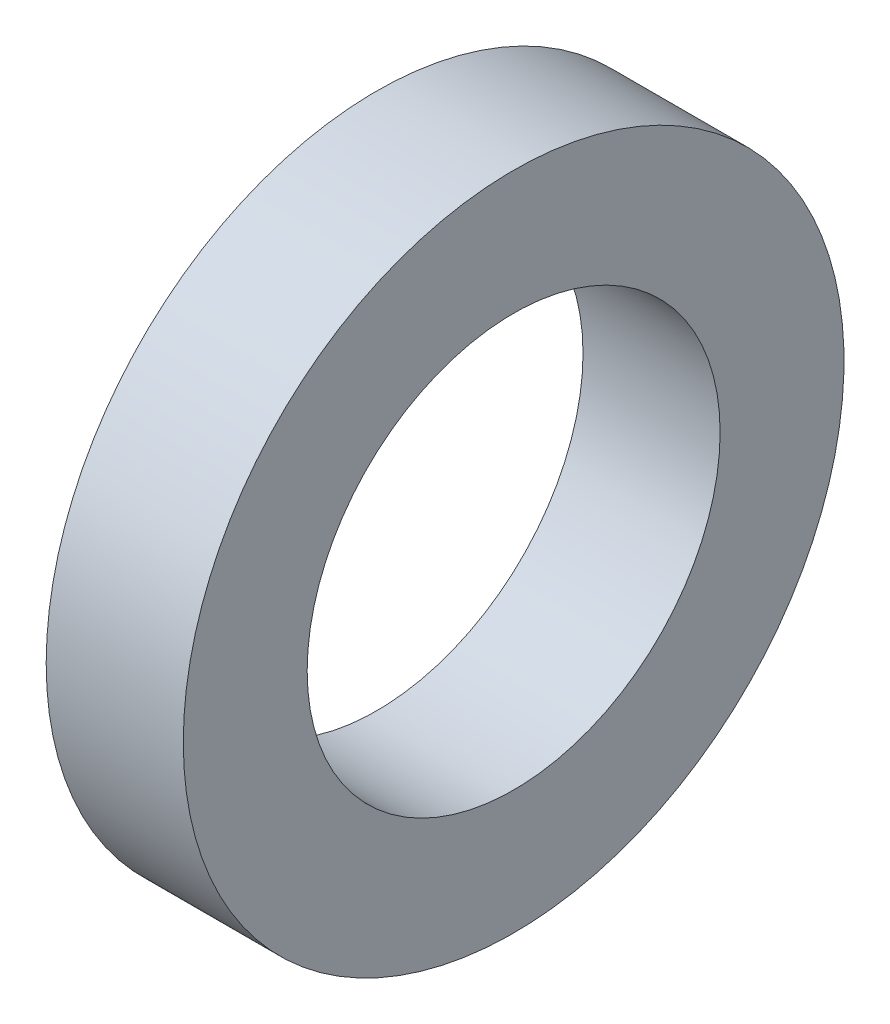
SolidWorks part; units mm, degrees
ref_plane "Front Plane" through (0, 0, 0) normal (0, 0, 1) x (1, 0, 0)
ref_plane "Top Plane" through (0, 0, 0) normal (0, 1, 0) x (1, 0, 0)
ref_plane "Right Plane" through (0, 0, 0) normal (1, 0, 0) x (0, 0, -1)
sketch "Sketch2" plane through (0, 0, 0) normal (0, 0, 1) x (1, 0, 0)
  line L0 (0, 0) -> (58.591, 0) construction
  line L2 (0, 0) -> (18.4, 0)
  line L3 (0, 0) -> (0, 2.5)
  line L4 (0, 2.5) -> (18.4, 2.5)
  line L5 (18.4, 0) -> (18.4, 2.5)
  line L6 (6.0094, 2.5) -> (6.0094, 6)
  line L11 (6.0094, 6) -> (9.9794, 6)
  line L16 (12.9794, 6) -> (12.9794, 3)
  line L17 (12.9794, 3) -> (13.6398, 3)
  line L18 (13.6398, 3) -> (13.6398, 2.5)
  line L19 (13.6398, 2.5) -> (6.0094, 2.5)
  line L22 (13.6398, 2.5) -> (16.1198, 2.5)
  line L23 (13.6398, 2.5) -> (13.6398, 4)
  line L24 (13.6398, 4) -> (16.1198, 4)
  line L25 (16.1198, 2.5) -> (16.1198, 4)
  line L27 (6.0094, 6) -> (9.9794, 6)
  line L28 (6.0094, 6) -> (6.0094, 9)
  line L29 (6.0094, 9) -> (9.9794, 9)
  line L30 (9.9794, 6) -> (9.9794, 9)
  line L31 (6.0094, 9) -> (6.0094, 8.25)
  line L32 (6.0094, 8.25) -> (5.0094, 8.25)
  line L33 (8.6609, 22.001) -> (8.6609, 12.476) construction
  line L34 (5.0094, 12.476) -> (12.3124, 12.476)
  line L35 (9.9794, 9) -> (12.3124, 9)
  line L36 (5.0094, 7.9375) -> (1.8344, 7.9375)
  line L37 (5.0094, 8.25) -> (5.0094, 12.476)
  line L38 (5.0094, 7.9375) -> (5.0094, 13.9365)
  line L39 (5.0094, 13.9365) -> (1.8344, 13.9365)
  line L40 (1.8344, 7.9375) -> (1.8344, 13.9365)
  line L41 (5.0094, 22.001) -> (12.3124, 22.001)
  line L42 (5.0094, 22.001) -> (5.0094, 30.1625)
  line L43 (5.0094, 30.1625) -> (12.3124, 30.1625)
  line L44 (12.3124, 22.001) -> (12.3124, 30.1625)
  line L49 (16.6398, 22.001) -> (16.6398, 7.5)
  line L51 (23.0198, 7.5) -> (23.0198, 6.5)
  line L54 (16.1198, 4) -> (13.6398, 4)
  line L56 (18.0398, 7.5) -> (23.0198, 7.5)
  line L57 (13.3124, 22.001) -> (16.6398, 22.001)
  line L58 (16.1198, 3.5) -> (20.0198, 3.5)
  line L59 (29.9098, 14) -> (26.9098, 11)
  line L60 (4.0094, 31.75) -> (18.0398, 31.75)
  line L61 (18.0398, 7.5) -> (23.0198, 7.5)
  line L62 (18.0398, 7.5) -> (18.0398, 12)
  line L63 (18.0398, 12) -> (23.0198, 12)
  line L64 (23.0198, 7.5) -> (23.0198, 12)
  line L65 (18.0398, 31.75) -> (18.0398, 12)
  line L66 (23.0198, 11) -> (26.9098, 11)
  line L67 (34.8098, 23) -> (31.3098, 19.5)
  line L68 (35.8098, 31) -> (38.7998, 33.99)
  line L69 (29.9098, 14) -> (29.9098, 15)
  line L70 (29.9098, 15) -> (22.9398, 15)
  line L71 (22.9398, 15) -> (21.0398, 15)
  line L72 (18.0398, 7.5) -> (16.6398, 7.5)
  line L73 (21.0398, 15) -> (21.0398, 43)
  line L74 (19.5798, 40) -> (9.6198, 40)
  line L75 (9.6198, 40) -> (4.0094, 40)
  line L76 (21.0398, 43) -> (19.5798, 43)
  line L77 (22.9398, 15) -> (29.9098, 15)
  line L78 (22.9398, 15) -> (22.9398, 21)
  line L79 (22.9398, 21) -> (29.9098, 21)
  line L80 (29.9098, 15) -> (29.9098, 21)
  line L81 (9.6198, 40) -> (19.5798, 40)
  line L82 (9.6198, 40) -> (9.6198, 50)
  line L83 (9.6198, 50) -> (19.5798, 50)
  line L84 (19.5798, 40) -> (19.5798, 50)
  line L85 (4.0094, 40) -> (4.0094, 31.75)
  line L86 (12.9794, 3) -> (12.9794, 2.5)
  line L87 (31.3098, 19.5) -> (29.9098, 19.5)
  line L88 (21.4694, 63.5) -> (21.4694, 51.308)
  line L89 (21.4694, 63.5) -> (25.9398, 63.5)
  line L90 (25.9398, 63.5) -> (25.9398, 25)
  line L91 (27.8398, 25) -> (25.9398, 25)
  line L92 (9.6198, 48) -> (8.1598, 48)
  line L93 (8.1598, 48) -> (8.1598, 53.476)
  line L94 (8.1598, 53.476) -> (19.5798, 53.476)
  line L95 (19.5798, 53.476) -> (19.5798, 50)
  line L96 (13.8698, 63.001) -> (13.8698, 53.476) construction
  line L97 (8.1598, 63.001) -> (19.5798, 63.001)
  line L98 (8.1598, 63.001) -> (8.1598, 68.2625)
  line L99 (8.1598, 68.2625) -> (19.5798, 68.2625)
  line L100 (19.5798, 63.001) -> (19.5798, 68.2625)
  line L101 (12.9794, 6) -> (11.9794, 6)
  line L102 (8.1598, 44.825) -> (4.9848, 44.825)
  line L103 (8.1598, 44.825) -> (8.1598, 54.9365)
  line L104 (8.1598, 54.9365) -> (4.9848, 54.9365)
  line L106 (9.9794, 6) -> (10.8794, 6)
  line L107 (27.8398, 25) -> (34.8098, 25)
  line L108 (34.8098, 25) -> (34.8098, 23)
  line L109 (0, 0) -> (-2, 0)
  line L110 (0, 0) -> (0, 11)
  line L111 (27.8398, 25) -> (34.8098, 25)
  line L112 (27.8398, 25) -> (27.8398, 32.5)
  line L113 (27.8398, 32.5) -> (34.8098, 32.5)
  line L114 (34.8098, 25) -> (34.8098, 32.5)
  line L115 (35.8098, 31) -> (34.8098, 31)
  line L116 (27.8398, 32.5) -> (27.8398, 64.5)
  line L117 (20.5373, 74.025) -> (6.2023, 74.025)
  line L118 (6.2023, 74.025) -> (6.2023, 76.2)
  line L119 (38.7998, 47.29) -> (30.8398, 55.25)
  line L120 (0, 11) -> (-2, 11)
  line L121 (38.7998, 43.815) -> (30.8623, 43.815)
  line L123 (-4.8152, 69.85) -> (1.5348, 76.2)
  line L124 (38.7998, 47.29) -> (38.7998, 33.99)
  line L125 (-2, 0) -> (-2, 11)
  line L126 (38.7998, 37.465) -> (30.8623, 37.465)
  line L127 (30.8623, 43.815) -> (30.8623, 37.465)
  line L128 (6.0094, 2.5) -> (6.0094, 0)
  line L129 (-0.0152, 63.5) -> (-0.0152, 30)
  line L132 (4.9848, 63.5) -> (-0.0152, 63.5)
  line L136 (-1.8152, 30) -> (-11.7752, 30)
  line L138 (-13.7752, 25.4) -> (-2, 25.4)
  line L139 (-2, 25.4) -> (-2, 11.5)
  line L140 (27.8398, 64.5) -> (20.5373, 64.5)
  line L141 (-1.8152, 30) -> (-11.7752, 30)
  line L142 (-1.8152, 30) -> (-1.8152, 39)
  line L143 (-1.8152, 39) -> (-11.7752, 39)
  line L144 (-11.7752, 30) -> (-11.7752, 39)
  line L145 (20.5373, 64.5) -> (20.5373, 74.025)
  line L146 (-12.7752, 37) -> (-12.7752, 47.29)
  line L147 (-12.7752, 37) -> (-11.7752, 37)
  line L148 (30.8398, 55.25) -> (30.8398, 76.2)
  line L149 (11.9794, 6) -> (11.9794, 5.45)
  line L154 (-2, 11.5) -> (0.5, 11.5)
  line L155 (4.9848, 60.6197) -> (24.0348, 60.6197)
  line L160 (4.9848, 60.6197) -> (4.9848, 55.8572)
  line L161 (4.9848, 55.8572) -> (24.0348, 55.8572)
  line L166 (24.0348, 60.6197) -> (24.0348, 55.8572)
  line L167 (4.9848, 60.6197) -> (24.0348, 55.8572) construction
  line L172 (4.9848, 55.8572) -> (24.0348, 60.6197) construction
  line L173 (24.0348, 62.2072) -> (25.9398, 62.2072)
  line L174 (11.9794, 5.45) -> (10.8794, 5.45)
  line L175 (10.8794, 6) -> (10.8794, 5.45)
  line L176 (24.0348, 62.2072) -> (24.0348, 54.2697)
  line L177 (24.0348, 54.2697) -> (25.9398, 54.2697)
  line L178 (25.9398, 62.2072) -> (25.9398, 54.2697)
  line L179 (24.0348, 62.2072) -> (25.9398, 54.2697) construction
  line L180 (24.0348, 54.2697) -> (25.9398, 62.2072) construction
  line L181 (3, 19.6197) -> (15.7, 19.6197)
  line L182 (3, 19.6197) -> (3, 14.8572)
  line L183 (3, 14.8572) -> (15.7, 14.8572)
  line L184 (15.7, 19.6197) -> (15.7, 14.8572)
  line L185 (3, 19.6197) -> (15.7, 14.8572) construction
  line L186 (3, 14.8572) -> (15.7, 19.6197) construction
  line L187 (15.7, 21.2072) -> (16.6398, 21.2072)
  line L188 (15.7, 21.2072) -> (15.7, 13.2697)
  line L189 (15.7, 13.2697) -> (16.6398, 13.2697)
  line L190 (16.6398, 21.2072) -> (16.6398, 13.2697)
  line L191 (15.7, 21.2072) -> (16.6398, 13.2697) construction
  line L192 (15.7, 13.2697) -> (16.6398, 21.2072) construction
  line L193 (0.5, 11.5) -> (0.5, 6.9375)
  line L194 (0.5, 6.9375) -> (1.8344, 6.9375)
  line L195 (23.0198, 6.5) -> (20.0198, 3.5)
  line L196 (4.9848, 63.5) -> (4.9848, 54.9365)
  line L197 (3, 43.825) -> (4.9848, 43.825)
  line L198 (1.8344, 6.9375) -> (1.8344, 7.9375)
  line L199 (6.0094, 0) -> (12.9794, 0)
  line L200 (12.9794, 0) -> (12.9794, 2.5)
  line L201 (18.0398, 31.75) -> (18.0398, 35.875)
  line L202 (18.0398, 35.875) -> (21.0398, 35.875)
  line L203 (30.8398, 76.2) -> (6.2023, 76.2)
  line L204 (2.7573, 69.85) -> (7.2023, 69.85) construction
  line L205 (7.2023, 67.4688) -> (26.2523, 67.4688)
  line L206 (7.2023, 74.025) -> (7.2023, 64.5)
  line L207 (7.2023, 64.5) -> (-1.8152, 64.5)
  line L208 (-1.8152, 64.5) -> (-1.8152, 39)
  line L209 (-12.7752, 47.29) -> (-4.8152, 55.25)
  line L210 (-4.8152, 55.25) -> (-4.8152, 69.85)
  line L211 (7.2023, 67.4688) -> (7.2023, 72.2312)
  line L212 (7.2023, 72.2312) -> (26.2523, 72.2313)
  line L213 (26.2523, 67.4688) -> (26.2523, 72.2313)
  line L214 (26.2523, 73.8187) -> (30.8398, 73.8187)
  line L215 (26.2523, 73.8187) -> (26.2523, 65.8813)
  line L216 (26.2523, 65.8813) -> (30.8398, 65.8813)
  line L217 (30.8398, 73.8187) -> (30.8398, 65.8813)
  line L218 (2.7573, 72.2313) -> (24.9823, 72.2313)
  line L219 (2.7573, 72.2313) -> (2.7573, 67.4687)
  line L220 (2.7573, 67.4687) -> (24.9823, 67.4687)
  line L221 (24.9823, 72.2313) -> (24.9823, 67.4687)
  line L222 (24.9823, 69.85) -> (20.5373, 69.85) construction
  line L223 (21.4694, 51.308) -> (22.9398, 51.308)
  line L224 (22.9398, 51.308) -> (22.9398, 21)
  line L225 (13.6398, 4) -> (13.6398, 12.2697)
  line L226 (13.6398, 12.2697) -> (13.3124, 12.2697)
  line L227 (13.3124, 12.2697) -> (13.3124, 22.001)
  line L228 (12.3124, 9) -> (12.3124, 12.476)
  line L229 (-1.8152, 30) -> (-0.0152, 30)
  line L230 (8.1598, 65.6317) -> (2.7573, 65.6317) construction
  line L231 (19.5798, 65.6317) -> (24.9823, 65.6317) construction
  line L232 (1.5348, 76.2) -> (6.2023, 76.2)
  line L233 (-11.7752, 30) -> (-13.7752, 30)
  line L234 (-13.7752, 30) -> (-13.7752, 25.4)
  line L235 (3, 13.9365) -> (3, 43.825)
  line L236 (4.9848, 54.9365) -> (4.9848, 44.825)
  line L237 (4.9848, 43.825) -> (4.9848, 44.825)
  circle A0 centre (26.8898, 25.95) radius 0.95
  circle A1 centre (21.9898, 15.95) radius 0.95
  circle A2 centre (17.3398, 8.2) radius 0.7
  circle A3 centre (10.4294, 6.45) radius 0.45
  circle A4 centre (-0.9152, 30.9) radius 0.9
  point P7 (24.9873, 58.2385)
  point P131 (16.1699, 17.2385)
  point P135 (14.5098, 58.2385)
  point P146 (9.35, 17.2385)
sketch "Sketch3" plane through (0, 0, 0) normal (0, 0, 1) x (1, 0, 0)
  line L0 (18.0398, 12) -> (23.0198, 12) construction
  line L1 (18.0398, 7.5) -> (23.0198, 7.5) construction
  line L2 (18.0398, 7.5) -> (18.0398, 12) construction
  line L3 (23.0198, 7.5) -> (23.0198, 12) construction
  line L4 (18.0398, 12) -> (23.0198, 12)
  line L5 (18.0398, 7.5) -> (23.0198, 7.5)
  line L6 (18.0398, 7.5) -> (18.0398, 12)
  line L7 (23.0198, 7.5) -> (23.0198, 12)
revolve "Revolve1" add sketch "Sketch3" angle 360 about L0
